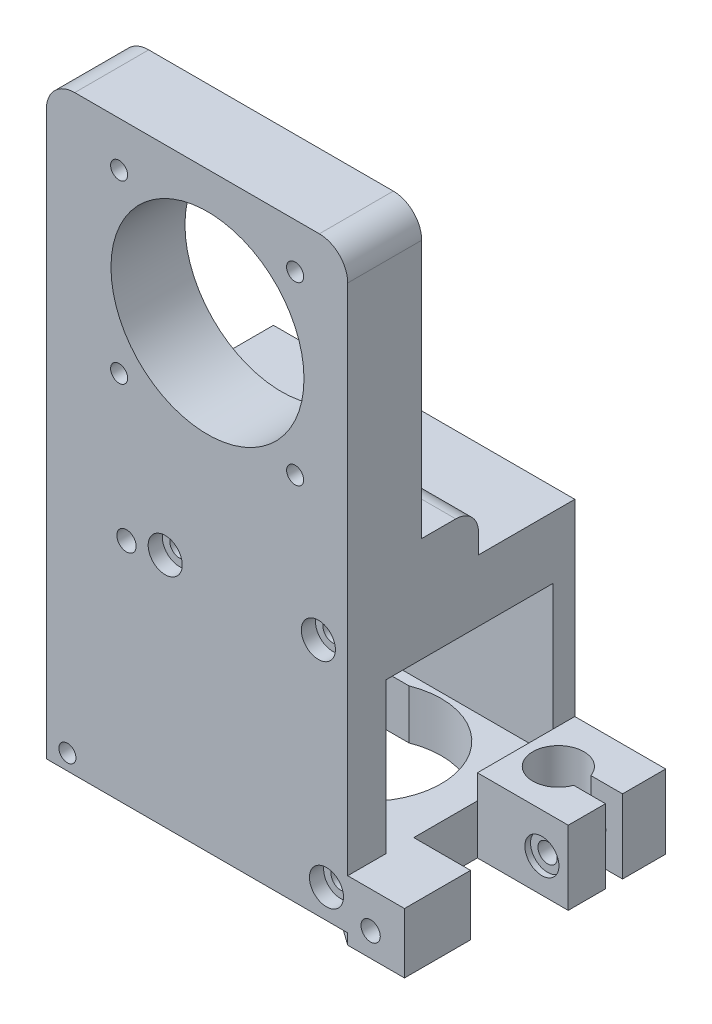
SolidWorks part; units mm, degrees
ref_plane "Front Plane" through (0, 0, 0) normal (0, 0, 1) x (1, 0, 0)
ref_plane "Top Plane" through (0, 0, 0) normal (0, 1, 0) x (1, 0, 0)
ref_plane "Right Plane" through (0, 0, 0) normal (1, 0, 0) x (0, 0, -1)
sketch "Sketch1" plane through (0, 0, 0) normal (0, 0, 1) x (1, 0, 0)
  line L1 (-22.5, 22.5) -> (22.5, 22.5)
  line L2 (-22.5, 22.5) -> (-22.5, -22.5)
  line L3 (-22.5, -22.5) -> (22.5, -22.5)
  line L4 (22.5, 22.5) -> (22.5, -22.5)
  line L5 (-22.5, 22.5) -> (22.5, -22.5) construction
  line L6 (-22.5, -22.5) -> (22.5, 22.5) construction
  point P0 (0, 0)
  dimension "D1" = 45
  dimension "D2" = 45
extrude "Boss-Extrude1" add sketch "Sketch1" along normal blind 35
sketch "Sketch2" plane through (0, 0, 35) normal (0, 0, 1) x (1, 0, 0)
  circle A0 centre (0, 0) radius 13
extrude "Cut-Extrude3" cut sketch "Sketch2" against normal blind 35
sketch "Sketch4" plane through (0, 0, 0) normal (0, 0, -1) x (-1, 0, 0)
  circle A0 centre (-15.8089, 15.9288) radius 1.7
sketch "Sketch5" plane through (0, 0, 0) normal (0, 0, -1) x (-1, 0, 0)
  circle A0 centre (-15.7813, -15.0653) radius 1.7
sketch "Sketch6" plane through (0, 0, 0) normal (0, 0, -1) x (-1, 0, 0)
  circle A0 centre (15.2203, -15.0657) radius 1.7
sketch "Sketch7" plane through (0, 0, 0) normal (0, 0, -1) x (-1, 0, 0)
  circle A0 centre (15.2, 15.9234) radius 1.7
extrude "Cut-Extrude8" cut sketch "Sketch4" against normal blind 35 contours A0
extrude "Cut-Extrude9" cut sketch "Sketch7" against normal blind 35 contours A0
extrude "Cut-Extrude10" cut sketch "Sketch6" against normal blind 35 contours A0
extrude "Cut-Extrude11" cut sketch "Sketch5" against normal blind 35 contours A0
sketch "Sketch8" plane through (22.5, 0, 0) normal (1, 0, 0) x (0, 0, -1)
  line L0 (-4.3639, -12.0361) -> (-35, -12.0361)
  line L2 (-35, -22.5) -> (-35, 22.5) construction
  line L3 (-35, -12.0361) -> (-35, 22.5)
  line L4 (-35, 22.5) -> (-8.4231, 22.5)
  line L5 (-35, 22.5) -> (0, 22.5) construction
  line L6 (-8.4231, 22.5) -> (-8.4231, 12.9255)
  line L7 (-8.4231, 12.9255) -> (-4.3639, 12.9255)
  line L8 (-4.3639, 12.9255) -> (-4.3639, -12.0361)
extrude "Cut-Extrude12" cut sketch "Sketch8" against normal blind 12
sketch "Sketch14" plane through (0, 22.5, 0) normal (0, 1, 0) x (1, 0, 0)
  line L1 (3.1909, -14.7293) -> (9.1909, -14.7293)
  line L2 (3.1909, -14.7293) -> (3.1909, -20.7293)
  line L3 (3.1909, -20.7293) -> (9.1909, -20.7293)
  line L4 (9.1909, -14.7293) -> (9.1909, -20.7293)
  line L5 (3.1909, -14.7293) -> (9.1909, -20.7293) construction
  line L6 (3.1909, -20.7293) -> (9.1909, -14.7293) construction
  point P0 (6.1909, -17.7293)
extrude "Boss-Extrude4" add sketch "Sketch14" along normal blind 2 and the other way blind 37.5
sketch "Sketch20" plane through (0, 24.5, 0) normal (0, 1, 0) x (1, 0, 0)
  line L0 (3.1909, -20.7293) -> (9.1909, -14.7293) construction
  circle A0 centre (6.1909, -17.7293) radius 2.2
  dimension "D1" = 4.4
extrude "Cut-Extrude17" cut sketch "Sketch20" against normal blind 7 and the other way through all contours A0
sketch "Sketch21" plane through (0, 17.5, 0) normal (0, 1, 0) x (1, 0, 0)
  circle A0 centre (6.1909, -17.7293) radius 1.75
extrude "Cut-Extrude18" cut sketch "Sketch21" against normal blind 2
ref_plane "Plane6" through (0, 16.5, 0) normal (0, 1, 0) x (1, 0, 0)
mirror "Mirror6" about plane through (0, 16.5, 0) normal (0, 1, 0) of "Cut-Extrude17"
sketch "Sketch22" plane through (0, -22.5, 0) normal (0, -1, 0) x (1, 0, 0)
  line L1 (-28.0826, 40.0025) -> (25, 40.0025)
  line L2 (-28.0826, 40.0025) -> (-28.0826, 0)
  line L3 (-28.0826, 0) -> (25, 0)
  line L4 (25, 40.0025) -> (25, 0)
  line L5 (-28.0826, 40.0025) -> (25, 0) construction
  line L6 (-28.0826, 0) -> (25, 40.0025) construction
  point P0 (-1.5413, 20.0013)
extrude "Boss-Extrude5" add sketch "Sketch22" along normal blind 44.5712 and the other way blind 1.5626
sketch "Sketch23" plane through (-28.0826, 0, 0) normal (-1, 0, 0) x (0, 0, 1)
  line L1 (3.8043, -58.359) -> (33.254, -58.359)
  line L2 (3.8043, -58.359) -> (3.8043, -31.8415)
  line L3 (3.8043, -31.8415) -> (33.254, -31.8415)
  line L4 (33.254, -58.359) -> (33.254, -31.8415)
  line L5 (3.8043, -58.359) -> (33.254, -31.8415) construction
  line L6 (3.8043, -31.8415) -> (33.254, -58.359) construction
  point P0 (18.5291, -45.1003)
extrude "Cut-Extrude19" cut sketch "Sketch23" against normal through all
sketch "Sketch25" plane through (0, -20.9374, 0) normal (0, 1, 0) x (1, 0, 0)
  circle A0 centre (6.1909, -17.7293) radius 5
extrude "Cut-Extrude24" cut sketch "Sketch25" against normal blind 2.6
sketch "Sketch26" plane through (0, -23.5374, 0) normal (0, 1, 0) x (1, 0, 0)
  circle A0 centre (6.1909, -17.7293) radius 8.1
extrude "Cut-Extrude25" cut sketch "Sketch26" against normal blind 4 contours A0
sketch "Sketch27" plane through (0, -27.5374, 0) normal (0, 1, 0) x (1, 0, 0)
  circle A0 centre (6.1909, -17.7293) radius 6.7
extrude "Cut-Extrude28" cut sketch "Sketch27" against normal blind 6
sketch "Sketch30" plane through (0, -58.359, 0) normal (0, 1, 0) x (1, 0, 0)
  circle A0 centre (6.2079, -17.7293) radius 13
extrude "Cut-Extrude30" cut sketch "Sketch30" against normal blind 10.7676
sketch "Sketch31" plane through (0, -67.0712, 0) normal (0, -1, 0) x (1, 0, 0)
  line L1 (-17.2669, 29.2843) -> (2.0826, 29.2843)
  line L2 (-17.2669, 29.2843) -> (-17.2669, 5.6402)
  line L3 (-17.2669, 5.6402) -> (2.0826, 5.6402)
  line L4 (2.0826, 29.2843) -> (2.0826, 5.6402)
  line L5 (-17.2669, 29.2843) -> (2.0826, 5.6402) construction
  line L6 (-17.2669, 5.6402) -> (2.0826, 29.2843) construction
  point P0 (-7.5922, 17.4622)
extrude "Cut-Extrude31" cut sketch "Sketch31" against normal blind 9.6643
sketch "Sketch34" plane through (-28.0826, 0, 0) normal (-1, 0, 0) x (0, 0, 1)
  circle A4 centre (35.5309, -28.495) radius 1.5
  circle A5 centre (3.5309, -28.495) radius 1.5
  circle A6 centre (35.5309, -60.495) radius 1.5
  circle A7 centre (3.5309, -60.495) radius 1.5
extrude "Cut-Extrude32" cut sketch "Sketch34" against normal blind 9 contours A5 | A7 | A6 | A4
sketch "Sketch37" plane through (25, 0, 0) normal (1, 0, 0) x (0, 0, -1)
  line L1 (-28.3675, -68.9589) -> (-40.0025, -68.9589)
  line L2 (-28.3675, -68.9589) -> (-28.3675, -58.359)
  line L3 (-28.3675, -58.359) -> (-40.0025, -58.359)
  line L4 (-40.0025, -68.9589) -> (-40.0025, -58.359)
  line L5 (-28.3675, -68.9589) -> (-40.0025, -58.359) construction
  line L6 (-28.3675, -58.359) -> (-40.0025, -68.9589) construction
  point P0 (-34.185, -63.659)
extrude "Boss-Extrude6" add sketch "Sketch37" along normal blind 10 and the other way blind 5 draft 29
sketch "Sketch38" plane through (0, 0, 40.0025) normal (0, 0, 1) x (1, 0, 0)
  circle A0 centre (29.0349, -64.7484) radius 1.7
extrude "Cut-Extrude33" cut sketch "Sketch38" against normal blind 10 contours A0
sketch "Sketch39" plane through (0, 0, 40.0025) normal (0, 0, 1) x (1, 0, 0)
  circle A0 centre (-13.9651, -26.7484) radius 1.7
extrude "Cut-Extrude34" cut sketch "Sketch39" against normal through all contours A0
sketch "Sketch40" plane through (25, 0, 0) normal (1, 0, 0) x (0, 0, -1)
  line L0 (0, -67.0712) -> (-28.3675, -67.0712) construction
  line L1 (-17.1599, -54.0712) -> (0, -54.0712)
  line L2 (-17.1599, -54.0712) -> (-17.1599, -67.0712)
  line L3 (-17.1599, -67.0712) -> (0, -67.0712)
  line L4 (0, -54.0712) -> (0, -67.0712)
  line L5 (-17.1599, -54.0712) -> (0, -67.0712) construction
  line L6 (-17.1599, -67.0712) -> (0, -54.0712) construction
  point P0 (-8.5799, -60.5712)
extrude "Boss-Extrude7" add sketch "Sketch40" along normal blind 16 contours L2 L3 L4 L1
sketch "Sketch41" plane through (0, -54.0712, 1.2693) normal (0, 1, 0) x (1, 0, 0)
  circle A0 centre (31.1639, -7.7934) radius 4.5
extrude "Cut-Extrude35" cut sketch "Sketch41" against normal blind 15 contours A0
sketch "Sketch42" plane through (0, -54.0712, 0) normal (0, 1, 0) x (1, 0, 0)
  line L1 (33.5282, -7.5957) -> (42.8596, -7.5957)
  line L2 (33.5282, -7.5957) -> (33.5282, -10.5957)
  line L3 (33.5282, -10.5957) -> (42.8596, -10.5957)
  line L4 (42.8596, -7.5957) -> (42.8596, -10.5957)
  line L5 (33.5282, -7.5957) -> (42.8596, -10.5957) construction
  line L6 (33.5282, -10.5957) -> (42.8596, -7.5957) construction
  point P0 (38.1939, -9.0957)
extrude "Cut-Extrude36" cut sketch "Sketch42" against normal blind 15
sketch "Sketch43" plane through (0, 0, 0) normal (0, 0, -1) x (-1, 0, 0)
  line L1 (-34.6289, -64.4039) -> (-32.7385, -61.0954)
  line L2 (-32.7385, -61.0954) -> (-34.6585, -57.804)
  line L3 (-34.6585, -57.804) -> (-38.4689, -57.821)
  line L4 (-38.4689, -57.821) -> (-40.3594, -61.1295)
  line L5 (-40.3594, -61.1295) -> (-38.4394, -64.421)
  line L6 (-38.4394, -64.421) -> (-34.6289, -64.4039)
  circle A1 centre (-36.5489, -61.1125) radius 3.3 construction
extrude "Cut-Extrude37" cut sketch "Sketch43" against normal blind 5
sketch "Sketch44" plane through (0, 0, 17.1599) normal (0, 0, 1) x (1, 0, 0)
  circle A0 centre (36.3605, -61.0871) radius 1.7
extrude "Cut-Extrude38" cut sketch "Sketch44" against normal blind 23 contours A0
sketch "Sketch48" plane through (0, 0, 0) normal (0, 0, -1) x (-1, 0, 0)
  line L1 (9.0667, -28.8111) -> (10.9572, -25.5026)
  line L2 (10.9572, -25.5026) -> (9.0372, -22.2111)
  line L3 (9.0372, -22.2111) -> (5.2267, -22.2282)
  line L4 (5.2267, -22.2282) -> (3.3362, -25.5367)
  line L5 (3.3362, -25.5367) -> (5.2563, -28.8281)
  line L6 (5.2563, -28.8281) -> (9.0667, -28.8111)
  circle A1 centre (7.1467, -25.5196) radius 3.3 construction
sketch "Sketch49" plane through (0, 0, 0) normal (0, 0, -1) x (-1, 0, 0)
  line L1 (-19.3395, -65.2659) -> (-17.449, -61.9575)
  line L2 (-17.449, -61.9575) -> (-19.369, -58.666)
  line L3 (-19.369, -58.666) -> (-23.1795, -58.6831)
  line L4 (-23.1795, -58.6831) -> (-25.07, -61.9916)
  line L5 (-25.07, -61.9916) -> (-23.15, -65.283)
  line L6 (-23.15, -65.283) -> (-19.3395, -65.2659)
  circle A1 centre (-21.2595, -61.9745) radius 3.3 construction
sketch "Sketch50" plane through (0, 0, 0) normal (0, 0, -1) x (-1, 0, 0)
  line L1 (-17.9116, -28.2435) -> (-16.0212, -24.935)
  line L2 (-16.0212, -24.935) -> (-17.9412, -21.6436)
  line L3 (-17.9412, -21.6436) -> (-21.7517, -21.6606)
  line L4 (-21.7517, -21.6606) -> (-23.6421, -24.9691)
  line L5 (-23.6421, -24.9691) -> (-21.7221, -28.2606)
  line L6 (-21.7221, -28.2606) -> (-17.9116, -28.2435)
  circle A1 centre (-19.8316, -24.9521) radius 3.3 construction
sketch "Sketch51" plane through (0, 0, 40.0025) normal (0, 0, 1) x (1, 0, 0)
  circle A0 centre (-7.1467, -25.5196) radius 1.7
sketch "Sketch52" plane through (0, 0, 40.0025) normal (0, 0, 1) x (1, 0, 0)
  circle A0 centre (19.8316, -24.9521) radius 1.7
sketch "Sketch53" plane through (0, 0, 40.0025) normal (0, 0, 1) x (1, 0, 0)
  circle A0 centre (21.2595, -61.9745) radius 1.7
extrude "Cut-Extrude39" cut sketch "Sketch48" against normal blind 5
extrude "Cut-Extrude40" cut sketch "Sketch49" against normal blind 5
extrude "Cut-Extrude41" cut sketch "Sketch50" against normal blind 5
extrude "Cut-Extrude42" cut sketch "Sketch53" against normal through all contours A0
extrude "Cut-Extrude43" cut sketch "Sketch52" against normal through all contours A0
extrude "Cut-Extrude44" cut sketch "Sketch51" against normal through all
sketch "Sketch55" plane through (0, 0, 0) normal (0, 0, -1) x (-1, 0, 0)
  line L1 (16.7453, -30.1645) -> (18.3136, -26.0487)
  line L2 (18.3136, -26.0487) -> (15.5334, -22.6326)
  line L3 (15.5334, -22.6326) -> (11.1849, -23.3323)
  line L4 (11.1849, -23.3323) -> (9.6166, -27.448)
  line L5 (9.6166, -27.448) -> (12.3967, -30.8642)
  line L6 (12.3967, -30.8642) -> (16.7453, -30.1645)
  circle A0 centre (13.9651, -26.7484) radius 3.8144 construction
extrude "Cut-Extrude46" cut sketch "Sketch55" against normal blind 5
sketch "Sketch57" plane through (0, 0, 40.0025) normal (0, 0, 1) x (1, 0, 0)
  circle A0 centre (-7.1467, -25.5196) radius 3
sketch "Sketch58" plane through (0, 0, 40.0025) normal (0, 0, 1) x (1, 0, 0)
  circle A0 centre (19.8316, -24.9521) radius 3
sketch "Sketch59" plane through (0, 0, 40.0025) normal (0, 0, 1) x (1, 0, 0)
  circle A0 centre (21.2595, -61.9745) radius 3
extrude "Cut-Extrude48" cut sketch "Sketch57" against normal blind 2.5
extrude "Cut-Extrude49" cut sketch "Sketch58" against normal blind 2.5 contours A0
extrude "Cut-Extrude50" cut sketch "Sketch59" against normal blind 2.5 contours A0
sketch "Sketch60" plane through (0, 0, 0) normal (0, 0, -1) x (-1, 0, 0)
  circle A0 centre (-15.8089, 15.9288) radius 3
  circle A1 centre (15.2, 15.9234) radius 3
  circle A2 centre (-15.7813, -15.0653) radius 3
  circle A3 centre (15.2203, -15.0657) radius 3
extrude "Cut-Extrude51" cut sketch "Sketch60" against normal blind 1
sketch "Sketch61" plane through (9.1909, 0, 0) normal (1, 0, 0) x (0, 0, -1)
  line L1 (-21.0836, 7.2178) -> (-14.5415, 7.2178)
  line L2 (-21.0836, 7.2178) -> (-21.0836, -6.8125)
  line L3 (-21.0836, -6.8125) -> (-14.5415, -6.8125)
  line L4 (-14.5415, 7.2178) -> (-14.5415, -6.8125)
  line L5 (-21.0836, 7.2178) -> (-14.5415, -6.8125) construction
  line L6 (-21.0836, -6.8125) -> (-14.5415, 7.2178) construction
  point P0 (-17.8126, 0.2026)
extrude "Cut-Extrude52" cut sketch "Sketch61" against normal blind 6.5 contours L3 L4 L1 L2
sketch "Sketch62" plane through (-22.5, 0, 0) normal (-1, 0, 0) x (0, 0, 1)
  circle A0 centre (9.4038, -7.1271) radius 1.7
sketch "Sketch63" plane through (-22.5, 0, 0) normal (-1, 0, 0) x (0, 0, 1)
  circle A0 centre (29.5162, -7.0688) radius 1.7
sketch "Sketch67" plane through (-22.5, -2.4684, 0) normal (-1, 0, 0) x (0, 0, 1)
  line L1 (26.7141, -1.4425) -> (32.3183, -1.4425)
  line L2 (26.7141, -1.4425) -> (26.7141, -10.4391)
  line L3 (26.7141, -10.4391) -> (32.3183, -10.4391)
  line L4 (32.3183, -1.4425) -> (32.3183, -10.4391)
  line L5 (26.7141, -1.4425) -> (32.3183, -10.4391) construction
  line L6 (26.7141, -10.4391) -> (32.3183, -1.4425) construction
  point P0 (29.5162, -5.9408)
extrude "Boss-Extrude8" add sketch "Sketch67" against normal blind 33
sketch "Sketch68" plane through (-22.5, -2.4684, 0) normal (-1, 0, 0) x (0, 0, 1)
  line L1 (6.6705, -1.2663) -> (12.2748, -1.2663)
  line L2 (6.6705, -1.2663) -> (6.6705, -10.6664)
  line L3 (6.6705, -10.6664) -> (12.2748, -10.6664)
  line L4 (12.2748, -1.2663) -> (12.2748, -10.6664)
  line L5 (6.6705, -1.2663) -> (12.2748, -10.6664) construction
  line L6 (6.6705, -10.6664) -> (12.2748, -1.2663) construction
  point P0 (9.4726, -5.9663)
extrude "Boss-Extrude9" add sketch "Sketch68" against normal blind 33
extrude "Cut-Extrude55" cut sketch "Sketch63" against normal through all contours A0
extrude "Cut-Extrude56" cut sketch "Sketch62" against normal through all contours A0
sketch "Sketch69" plane through (-22.5, 0, 0) normal (-1, 0, 0) x (0, 0, 1)
  circle A0 centre (9.4038, -7.1271) radius 3
  circle A1 centre (29.5162, -7.0688) radius 3
extrude "Cut-Extrude57" cut sketch "Sketch69" against normal blind 2.5
sketch "Sketch70" plane through (0, 0, 28.3675) normal (0, 0, -1) x (-1, 0, 0)
  line L1 (-25.0573, -66.8115) -> (-25.2594, -62.3352)
  line L2 (-25.2594, -62.3352) -> (-29.2371, -60.2722)
  line L3 (-29.2371, -60.2722) -> (-33.0125, -62.6853)
  line L4 (-33.0125, -62.6853) -> (-32.8104, -67.1616)
  line L5 (-32.8104, -67.1616) -> (-28.8328, -69.2246)
  line L6 (-28.8328, -69.2246) -> (-25.0573, -66.8115)
  circle A0 centre (-29.0349, -64.7484) radius 3.8805 construction
extrude "Cut-Extrude58" cut sketch "Sketch70" against normal blind 2.5
sketch "Sketch71" plane through (0, 0, 17.1599) normal (0, 0, 1) x (1, 0, 0)
  circle A0 centre (36.3605, -61.0871) radius 3
extrude "Cut-Extrude59" cut sketch "Sketch71" against normal blind 1 contours A0
sketch "Sketch73" plane through (0, 0, 40.0025) normal (0, 0, 1) x (1, 0, 0)
  circle A0 centre (-24.3693, -64.3228) radius 1.5
extrude "Cut-Extrude61" cut sketch "Sketch73" against normal blind 5
ref_plane "Plane7" through (0, 0, 17.7293) normal (0, 0, 1) x (1, 0, 0)
ref_plane "Plane8" through (0, -20.9374, 0) normal (0, 1, 0) x (1, 0, 0)
sketch "Sketch78" plane through (0, 0, 17.7293) normal (0, 0, 1) x (1, 0, 0)
  line L0 (25, -20.9374) -> (-28.0826, -20.9374) construction
  line L1 (-33.1226, -20.9374) -> (49.9762, -20.9374)
  line L2 (-33.1226, -20.9374) -> (-33.1226, -72.7681)
  line L3 (-33.1226, -72.7681) -> (49.9762, -72.7681)
  line L4 (49.9762, -20.9374) -> (49.9762, -72.7681)
sketch "Sketch79" plane through (0, -20.9374, 0) normal (0, 1, 0) x (1, 0, 0)
  line L1 (-52.1, -49.3859) -> (43.5589, -49.3859)
  line L2 (-52.1, -49.3859) -> (-52.1, 1.9049)
  line L3 (-52.1, 1.9049) -> (43.5589, 1.9049)
  line L4 (43.5589, -49.3859) -> (43.5589, 1.9049)
extrude "Cut-Extrude62" cut sketch "Sketch79" along normal blind 59 contours L1 L4 L3 L2
sketch "Sketch80" plane through (0, -20.9374, 0) normal (0, 1, 0) x (1, 0, 0)
  line L1 (25, -40.0025) -> (-28.0826, -40.0025)
  line L2 (25, -40.0025) -> (25, -26.9707)
  line L3 (25, -26.9707) -> (-28.0826, -26.9707)
  line L4 (-28.0826, -40.0025) -> (-28.0826, -26.9707)
  line L5 (25, -40.0025) -> (-28.0826, -26.9707) construction
  line L6 (25, -26.9707) -> (-28.0826, -40.0025) construction
  line L7 (25, 0) -> (25, -40.0025) construction
  line L8 (-28.0826, -40.0025) -> (-28.0826, 0) construction
  line L9 (25, -40.0025) -> (-28.0826, -40.0025) construction
  point P0 (-1.5413, -33.4866)
extrude "Boss-Extrude10" add sketch "Sketch80" along normal blind 58
fillet "Fillet1" radius 5 2 edges at (-28.0826, 37.0626, 33.4866) (25, 37.0626, 33.4866)
sketch "Sketch84" plane through (0, 0, 26.9707) normal (0, 0, -1) x (-1, 0, 0)
  circle A0 centre (-0.299, 13.6036) radius 17
extrude "Cut-Extrude63" cut sketch "Sketch84" against normal blind 22
sketch "Sketch85" plane through (0, 0, 40.0025) normal (0, 0, 1) x (1, 0, 0)
  circle A0 centre (15.7368, 29.1356) radius 1.5
  circle A1 centre (15.7368, -1.8644) radius 1.5
  circle A2 centre (-15.2632, -1.8644) radius 1.5
  circle A3 centre (-15.2632, 29.1356) radius 1.5
extrude "Cut-Extrude64" cut sketch "Sketch85" against normal blind 15
sketch "Sketch86" plane through (0, -20.9374, 0) normal (0, 1, 0) x (1, 0, 0)
  line L0 (25, -26.9707) -> (-28.0826, -26.9707) construction
  line L1 (-28.0826, -26.9707) -> (-14.3865, -26.9707)
  line L2 (-28.0826, -26.9707) -> (-28.0826, -16.9707)
  line L3 (-28.0826, -16.9707) -> (-14.3865, -16.9707)
  line L4 (-14.3865, -26.9707) -> (-14.3865, -16.9707)
extrude "Boss-Extrude11" add sketch "Sketch86" along normal blind 7.5
fillet "Fillet3" radius 3 1 edges at (-21.2346, -13.4374, 16.9707)
sketch "Sketch87" plane through (0, -20.9374, 0) normal (0, 1, 0) x (1, 0, 0)
  line L0 (25, -26.9707) -> (-14.3865, -26.9707) construction
  line L1 (25, -16.9707) -> (14.2343, -16.9707)
  line L2 (25, -16.9707) -> (25, -26.9707)
  line L3 (25, -26.9707) -> (14.2343, -26.9707)
  line L4 (14.2343, -16.9707) -> (14.2343, -26.9707)
  line L5 (-14.3865, -16.9707) -> (-28.0826, -16.9707) construction
  line L6 (25, 0) -> (25, -26.9707) construction
extrude "Boss-Extrude12" add sketch "Sketch87" along normal blind 7.5
sketch "Sketch89" plane through (0, -20.9374, 0) normal (0, 1, 0) x (1, 0, 0)
  line L1 (61.8406, -52.5891) -> (-70.6943, -52.5891)
  line L2 (61.8406, -52.5891) -> (61.8406, 20.0544)
  line L3 (61.8406, 20.0544) -> (-70.6943, 20.0544)
  line L4 (-70.6943, -52.5891) -> (-70.6943, 20.0544)
fillet "Fillet6" radius 4 1 edges at (19.6171, -13.4374, 16.9707)
